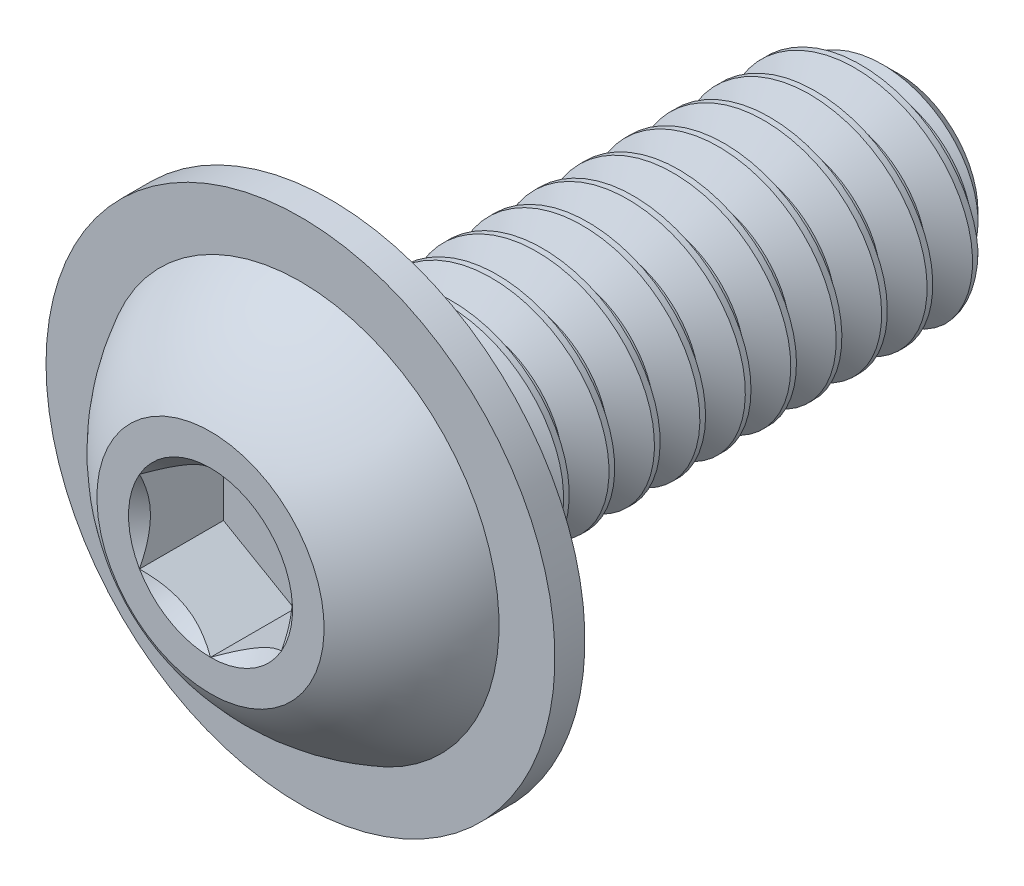
SolidWorks part; units mm, degrees
ref_plane "Front" through (0, 0, 0) normal (0, 0, 1) x (1, 0, 0)
ref_plane "Top" through (0, 0, 0) normal (0, 1, 0) x (1, 0, 0)
ref_plane "Right" through (0, 0, 0) normal (1, 0, 0) x (0, 0, -1)
sketch "Sketch1" plane through (0, 0, 0) normal (1, 0, 0) x (0, 0, -1)
  line L2 (3.3528, 3.175) -> (19.2278, 3.175)
  line L3 (19.2278, 3.175) -> (19.2278, 0)
  line L4 (19.2278, 0) -> (3.3528, 0)
  line L6 (2.5146, 5.5499) -> (3.3528, 5.5499) construction
  line L7 (19.2278, 3.175) -> (19.2278, -3.175) construction
  line L8 (0, 0) -> (3.3528, 0) construction
  line L9 (3.3528, 5.5499) -> (3.3528, -5.5499) construction
  line L11 (3.3528, 3.175) -> (3.3528, 0)
  line L13 (0, 1.9844) -> (0, -1.9844) construction
  line L14 (0, 1.9844) -> (0, 3.175) construction
  line L15 (2.5146, 5.5499) -> (2.5146, 7.112) construction
  line L16 (2.5146, 7.112) -> (3.3528, 7.112) construction
  line L17 (3.3528, 7.112) -> (3.3528, 5.5499) construction
  line L18 (3.3528, 7.112) -> (3.3528, -7.112) construction
  arc A3 (0, 3.175) -> (2.5146, 5.5499) centre (5.3774, 0) cw construction
  dimension "D1" = 0.8382
  dimension "Head Ht" = 3.3528
  dimension "Head Dia" = 11.0998
  dimension "Dia" = 6.35
  dimension "Lg" = 15.875
  dimension "Hex" = 3.9688
  dimension "Flange Dia" = 14.224
revolve "Revolve1" add sketch "Sketch1" angle 360 about L4
sketch "Sketch3" plane through (0, 0, -19.2278) normal (0, 0, -1) x (-1, 0, 0)
  circle A0 centre (0, 0) radius 3.175
curve "Helix/Spiral1" pitch 1.27 height 17.145 radius 3.175 centre (0, 0, -19.2278) axis (0, 0, 1) start towards (0, 1, 0)
sketch "Sketch2" plane through (0, 0, 0) normal (1, 0, 0) x (0, 0, -1)
  line L0 (19.2278, 3.175) -> (20.3391, 3.175)
  line L1 (20.3391, 3.175) -> (19.8628, 2.3501)
  line L2 (19.8628, 2.3501) -> (19.704, 2.3501)
  line L3 (19.704, 2.3501) -> (19.2278, 3.175)
  line L4 (19.4659, 2.7626) -> (20.1009, 2.7626) construction
  dimension "D1" = 60
  dimension "D2" = 0.1588
  dimension "D3" = 0.635
chamfer "Chamfer1" distance 0.9525 angle 45 1 edges at (0, 3.175, -19.2278)
sweep "Cut-Sweep1" cut profiles "Sketch2" path "Helix/Spiral1"
sketch "Sketch7" plane through (0, 0, 0) normal (1, 0, 0) x (0, 0, -1)
  line L6 (2.5146, 5.5499) -> (3.3528, 5.5499) construction
  line L8 (0, 0) -> (3.3528, 0) construction
  line L11 (3.3528, 5.5499) -> (3.3528, -5.5499) construction
  line L12 (2.5146, 5.5499) -> (3.3528, 5.5499)
  line L13 (0, 0) -> (3.3528, 0)
  line L14 (0, 1.9844) -> (0, -1.9844) construction
  line L15 (3.3528, 5.5499) -> (3.3528, 0)
  line L16 (0, 3.175) -> (0, 0)
  arc A2 (2.5146, 5.5499) -> (0, 3.175) centre (5.3774, 0) ccw construction
  arc A3 (2.5146, 5.5499) -> (0, 3.175) centre (5.3774, 0) ccw
revolve "Revolve2" add sketch "Sketch7" angle 360 about L13
sketch "Sketch11" plane through (0, 0, -3.3528) normal (0, 0, -1) x (-1, 0, 0)
  circle A0 centre (0, 0) radius 7.112
extrude "Boss-Extrude3" add sketch "Sketch11" against normal up to vertex (0.8382 mm away) up to point (0, 5.5499, -2.5146)
sketch "Sketch5" plane through (0, 0, 0) normal (0, 0, 1) x (1, 0, 0)
  line L1 (1.9844, -1.1457) -> (1.9844, 1.1457)
  line L2 (1.9844, 1.1457) -> (0, 2.2914)
  line L3 (0, 2.2914) -> (-1.9844, 1.1457)
  line L4 (-1.9844, 1.1457) -> (-1.9844, -1.1457)
  line L5 (-1.9844, -1.1457) -> (0, -2.2914)
  line L6 (0, -2.2914) -> (1.9844, -1.1457)
  circle A0 centre (0, 0) radius 1.9844 construction
extrude "Cut-Extrude2" cut sketch "Sketch5" against normal blind 2.347
sketch "Sketch6" plane through (0, 0, 0) normal (0, 0, 1) x (1, 0, 0)
  circle A0 centre (0, 0) radius 2.2914
extrude "Cut-Extrude3" cut sketch "Sketch6" against normal blind 2.347 draft 45
sketch "Sketch9" [suppressed] plane through (0, 0, -5.0546) normal (0, 0, 1) x (1, 0, 0)
  circle A2 centre (0, 0) radius 4.7625
extrude "Boss-Extrude2" [suppressed] add sketch "Sketch9" against normal offset from surface (6.35 mm away) 31.75 up to face at (0, 2.2225, -19.2278)
sketch "Sketch10" plane through (0, 0, 0) normal (1, 0, 0) x (0, 0, -1)
  line L0 (19.2278, 3.175) -> (19.2278, -3.175) construction
  point P0 (17.3228, -3.175)
  dimension "D1" = 1.905
equation "\"D3@Helix/Spiral1\" = \"Lg@Sketch1\" + \"D4@Helix/Spiral1\""
equation "\"D2@Sketch2\" = \"D4@Helix/Spiral1\" * .125"
equation "\"D3@Sketch2\" = \"D4@Helix/Spiral1\" * .5"
equation "\"D1@Chamfer1\" = \"D4@Helix/Spiral1\" * .75"
equation "\"D1@Cut-Extrude2\" = \"Head Ht@Sketch1\" * .7"
equation "\"D1@Sketch1\" = \"Head Ht@Sketch1\" * .25"
equation "\"D1@Sketch10\" = \"D4@Helix/Spiral1\" * 1.5"
equation "\"D1@Cut-Extrude3\" = \"D1@Cut-Extrude2\""
